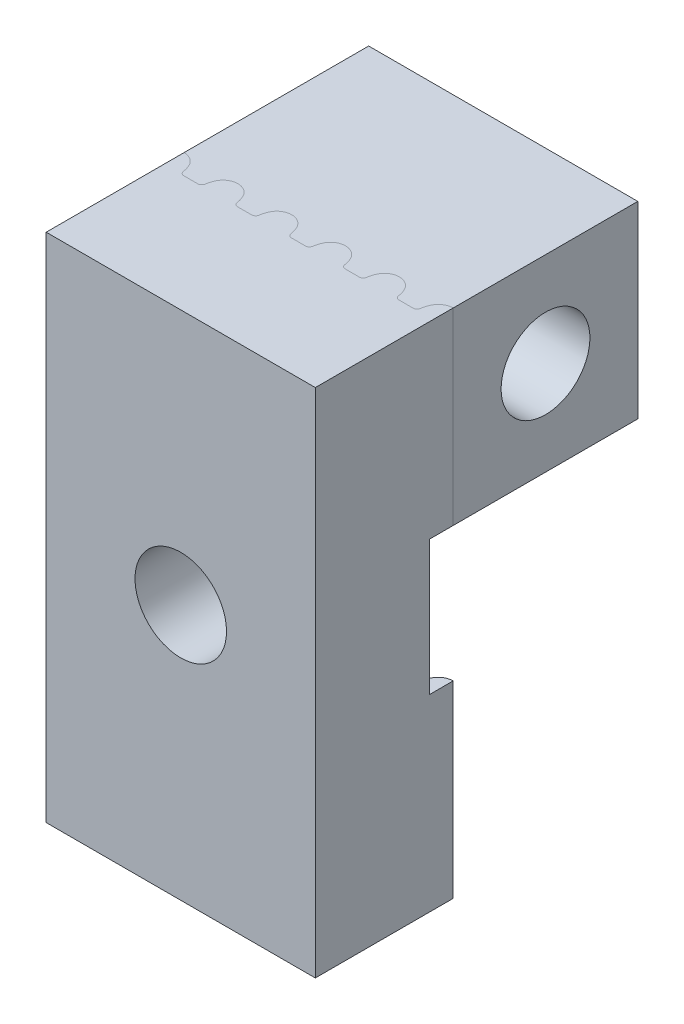
SolidWorks part; units mm, degrees
ref_plane "Front Plane" through (0, 0, 0) normal (0, 0, 1) x (1, 0, 0)
ref_plane "Top Plane" through (0, 0, 0) normal (0, 1, 0) x (1, 0, 0)
ref_plane "Right Plane" through (0, 0, 0) normal (1, 0, 0) x (0, 0, -1)
sketch "Sketch1" plane through (0, 0, 0) normal (0, 0, 1) x (1, 0, 0)
  line L1 (5, 9.5) -> (-5, 9.5)
  line L2 (5, 9.5) -> (5, -9.5)
  line L3 (5, -9.5) -> (-5, -9.5)
  line L4 (-5, 9.5) -> (-5, -9.5)
  line L5 (5, 9.5) -> (-5, -9.5) construction
  line L6 (5, -9.5) -> (-5, 9.5) construction
  point P0 (0, 0)
  dimension "D1" = 10
  dimension "D2" = 19
extrude "Boss-Extrude1" add sketch "Sketch1" along normal blind 4.25
hole_wizard "M3 Clearance Hole1" positions "Sketch3" profile "Sketch4" hole size "M3" standard "ANSI Metric" end condition through all
sketch "Sketch3" plane through (0, 0, 4.25) normal (0, 0, 1) x (1, 0, 0)
  point P0 (0, 0)
sketch "Sketch4" plane through (0, 0, 4.25) normal (1, 0, 0) x (0, -1, 0)
  line L0 (0, 0) -> (0, 4.25)
  line L1 (0, 4.25) -> (1.7, 4.25)
  line L2 (1.7, 4.25) -> (1.7, 0)
  line L5 (1.7, 0) -> (0, 0)
  line L11 (0, -6.35) -> (0, 107.95) construction
  dimension "Thru Hole Dia." = 3.4
  dimension "Thru Hole Depth" = 4.25
sketch "Sketch6" plane through (0, 9.5, 0) normal (0, 1, 0) x (1, 0, 0)
  line L0 (-5, 0) -> (-3, 0)
  line L1 (5, 0) -> (-5, 0) construction
  line L3 (-3.7421, 0.1225) -> (-4.2579, 0.1225)
  line L4 (-5, 0.1225) -> (-5, 0)
  line L5 (-5, 0.1225) -> (-5, 0.8725)
  line L6 (-4, 0) -> (-4, 0.5833) construction
  line L7 (-3, 0.1225) -> (-3, 0)
  line L8 (-3, 0.1225) -> (-3, 0.8725)
  arc A1 (-4.4065, 0.2522) -> (-4.5045, 0.5674) centre (-5.3973, 0.1171) ccw
  arc A2 (-4.5045, 0.5674) -> (-5, 0.8725) centre (-5, 0.3175) ccw
  arc A3 (-4.4065, 0.2522) -> (-4.2579, 0.1225) centre (-4.2579, 0.2725) ccw
  arc A4 (-3.5935, 0.2522) -> (-3.7421, 0.1225) centre (-3.7421, 0.2725) cw
  arc A5 (-3.5935, 0.2522) -> (-3.4955, 0.5674) centre (-2.6027, 0.1171) cw
  arc A6 (-3.4955, 0.5674) -> (-3, 0.8725) centre (-3, 0.3175) cw
  point P17 (-4, 0.1225)
  point P18 (-4, 0)
  dimension "D4" = 0.3
  dimension "D5" = 2
  dimension "D1" = 0.1225
  dimension "D2" = 1
  dimension "D3" = 0.75
  dimension "D6" = 0.1225
extrude "Boss-Extrude2" add sketch "Sketch6" against normal blind 7
pattern_linear "LPattern1" count 5 spacing 2 along (1, 0, 0) of "Boss-Extrude2"
mirror "Mirror1" about plane through (0, 0, 0) normal (0, 1, 0) of "LPattern1"
sketch "Sketch7" plane through (0, -9.5, 0) normal (0, -1, 0) x (1, 0, 0)
  line L5 (-5, -0.8725) -> (-5, -5.8725)
  line L6 (5, -0.8725) -> (5, -5.8725)
  line L7 (-5, -5.8725) -> (5, -5.8725)
  line L8 (-3.7421, -0.1225) -> (-4.2579, -0.1225) construction
  line L9 (-1.7421, -0.1225) -> (-2.2579, -0.1225) construction
  line L10 (0.2579, -0.1225) -> (-0.2579, -0.1225) construction
  line L11 (2.2579, -0.1225) -> (1.7421, -0.1225) construction
  line L12 (4.2579, -0.1225) -> (3.7421, -0.1225) construction
  line L13 (-3.7421, -0.1225) -> (-4.2579, -0.1225)
  line L14 (-1.7421, -0.1225) -> (-2.2579, -0.1225)
  line L15 (0.2579, -0.1225) -> (-0.2579, -0.1225)
  line L16 (2.2579, -0.1225) -> (1.7421, -0.1225)
  line L17 (4.2579, -0.1225) -> (3.7421, -0.1225)
  arc A26 (-5, -0.8725) -> (-4.5045, -0.5674) centre (-5, -0.3175) ccw construction
  arc A27 (-4.5045, -0.5674) -> (-4.4065, -0.2522) centre (-5.3973, -0.1171) ccw construction
  arc A28 (-4.2579, -0.1225) -> (-4.4065, -0.2522) centre (-4.2579, -0.2725) ccw construction
  arc A29 (-3.5935, -0.2522) -> (-3.7421, -0.1225) centre (-3.7421, -0.2725) ccw construction
  arc A30 (-3.5935, -0.2522) -> (-3.4955, -0.5674) centre (-2.6027, -0.1171) ccw construction
  arc A31 (-3.4955, -0.5674) -> (-2.5045, -0.5674) centre (-3, -0.3175) ccw construction
  arc A32 (-2.5045, -0.5674) -> (-2.4065, -0.2522) centre (-3.3973, -0.1171) ccw construction
  arc A33 (-2.2579, -0.1225) -> (-2.4065, -0.2522) centre (-2.2579, -0.2725) ccw construction
  arc A34 (-1.5935, -0.2522) -> (-1.7421, -0.1225) centre (-1.7421, -0.2725) ccw construction
  arc A35 (-1.5935, -0.2522) -> (-1.4955, -0.5674) centre (-0.6027, -0.1171) ccw construction
  arc A36 (-1.4955, -0.5674) -> (-0.5045, -0.5674) centre (-1, -0.3175) ccw construction
  arc A37 (-0.5045, -0.5674) -> (-0.4065, -0.2522) centre (-1.3973, -0.1171) ccw construction
  arc A38 (-0.2579, -0.1225) -> (-0.4065, -0.2522) centre (-0.2579, -0.2725) ccw construction
  arc A39 (0.4065, -0.2522) -> (0.2579, -0.1225) centre (0.2579, -0.2725) ccw construction
  arc A40 (0.4065, -0.2522) -> (0.5045, -0.5674) centre (1.3973, -0.1171) ccw construction
  arc A41 (0.5045, -0.5674) -> (1.4955, -0.5674) centre (1, -0.3175) ccw construction
  arc A42 (1.4955, -0.5674) -> (1.5935, -0.2522) centre (0.6027, -0.1171) ccw construction
  arc A43 (1.7421, -0.1225) -> (1.5935, -0.2522) centre (1.7421, -0.2725) ccw construction
  arc A44 (2.4065, -0.2522) -> (2.2579, -0.1225) centre (2.2579, -0.2725) ccw construction
  arc A45 (2.4065, -0.2522) -> (2.5045, -0.5674) centre (3.3973, -0.1171) ccw construction
  arc A46 (2.5045, -0.5674) -> (3.4955, -0.5674) centre (3, -0.3175) ccw construction
  arc A47 (3.4955, -0.5674) -> (3.5935, -0.2522) centre (2.6027, -0.1171) ccw construction
  arc A48 (3.7421, -0.1225) -> (3.5935, -0.2522) centre (3.7421, -0.2725) ccw construction
  arc A49 (4.4065, -0.2522) -> (4.2579, -0.1225) centre (4.2579, -0.2725) ccw construction
  arc A50 (4.4065, -0.2522) -> (4.5045, -0.5674) centre (5.3973, -0.1171) ccw construction
  arc A51 (4.5045, -0.5674) -> (5, -0.8725) centre (5, -0.3175) ccw construction
  arc A52 (-5, -0.8725) -> (-4.5045, -0.5674) centre (-5, -0.3175) ccw
  arc A53 (-4.5045, -0.5674) -> (-4.4065, -0.2522) centre (-5.3973, -0.1171) ccw
  arc A54 (-4.2579, -0.1225) -> (-4.4065, -0.2522) centre (-4.2579, -0.2725) ccw
  arc A55 (-3.5935, -0.2522) -> (-3.7421, -0.1225) centre (-3.7421, -0.2725) ccw
  arc A56 (-3.5935, -0.2522) -> (-3.4955, -0.5674) centre (-2.6027, -0.1171) ccw
  arc A57 (-3.4955, -0.5674) -> (-2.5045, -0.5674) centre (-3, -0.3175) ccw
  arc A58 (-2.5045, -0.5674) -> (-2.4065, -0.2522) centre (-3.3973, -0.1171) ccw
  arc A59 (-2.2579, -0.1225) -> (-2.4065, -0.2522) centre (-2.2579, -0.2725) ccw
  arc A60 (-1.5935, -0.2522) -> (-1.7421, -0.1225) centre (-1.7421, -0.2725) ccw
  arc A61 (-1.5935, -0.2522) -> (-1.4955, -0.5674) centre (-0.6027, -0.1171) ccw
  arc A62 (-1.4955, -0.5674) -> (-0.5045, -0.5674) centre (-1, -0.3175) ccw
  arc A63 (-0.5045, -0.5674) -> (-0.4065, -0.2522) centre (-1.3973, -0.1171) ccw
  arc A64 (-0.2579, -0.1225) -> (-0.4065, -0.2522) centre (-0.2579, -0.2725) ccw
  arc A65 (0.4065, -0.2522) -> (0.2579, -0.1225) centre (0.2579, -0.2725) ccw
  arc A66 (0.4065, -0.2522) -> (0.5045, -0.5674) centre (1.3973, -0.1171) ccw
  arc A67 (0.5045, -0.5674) -> (1.4955, -0.5674) centre (1, -0.3175) ccw
  arc A68 (1.4955, -0.5674) -> (1.5935, -0.2522) centre (0.6027, -0.1171) ccw
  arc A69 (1.7421, -0.1225) -> (1.5935, -0.2522) centre (1.7421, -0.2725) ccw
  arc A70 (2.4065, -0.2522) -> (2.2579, -0.1225) centre (2.2579, -0.2725) ccw
  arc A71 (2.4065, -0.2522) -> (2.5045, -0.5674) centre (3.3973, -0.1171) ccw
  arc A72 (2.5045, -0.5674) -> (3.4955, -0.5674) centre (3, -0.3175) ccw
  arc A73 (3.4955, -0.5674) -> (3.5935, -0.2522) centre (2.6027, -0.1171) ccw
  arc A74 (3.7421, -0.1225) -> (3.5935, -0.2522) centre (3.7421, -0.2725) ccw
  arc A75 (4.4065, -0.2522) -> (4.2579, -0.1225) centre (4.2579, -0.2725) ccw
  arc A76 (4.4065, -0.2522) -> (4.5045, -0.5674) centre (5.3973, -0.1171) ccw
  arc A77 (4.5045, -0.5674) -> (5, -0.8725) centre (5, -0.3175) ccw
  dimension "D1" = 5
extrude "Boss-Extrude4" add sketch "Sketch7" against normal up to surface (19 mm away) separate body up to face at (0, 9.5, -0.1114)
sketch "Sketch8" plane through (0, 0, -0.1225) normal (0, 0, 1) x (1, 0, 0)
  line L0 (-5, 9.5) -> (-5, -9.5) construction
  line L1 (5, 2.5) -> (-5, 2.5)
  line L2 (5, 2.5) -> (5, -2.5)
  line L3 (5, -2.5) -> (-5, -2.5)
  line L4 (-5, 2.5) -> (-5, -2.5)
  line L5 (5, 2.5) -> (-5, -2.5) construction
  line L6 (5, -2.5) -> (-5, 2.5) construction
  line L7 (-0.5045, 9.5) -> (-1.4955, 9.5) construction
  point P0 (0, 0)
  dimension "D1" = 7
extrude "Cut-Extrude1" cut sketch "Sketch8" against normal blind 0.75
hole_wizard "M3 Clearance Hole2" positions "Sketch10" profile "Sketch11" hole size "M3" standard "ANSI Metric" end condition through all
sketch "Sketch10" plane through (0, 0, -0.8725) normal (0, 0, 1) x (1, 0, 0)
  point P0 (0, 0)
sketch "Sketch11" plane through (0, 0, -0.8725) normal (1, 0, 0) x (0, -1, 0)
  line L0 (0, 0) -> (0, 5)
  line L1 (0, 5) -> (1.7, 5)
  line L2 (1.7, 5) -> (1.7, 0)
  line L5 (1.7, 0) -> (0, 0)
  line L11 (0, -6.35) -> (0, 107.95) construction
  dimension "Thru Hole Dia." = 3.4
  dimension "Thru Hole Depth" = 5
sketch "Sketch12" plane through (0, 0, -0.1225) normal (0, 0, 1) x (1, 0, 0)
  line L1 (-5, 2.5) -> (5, 2.5)
  line L2 (-5, 2.5) -> (-5, -9.5)
  line L3 (-5, -9.5) -> (5, -9.5)
  line L4 (5, 2.5) -> (5, -9.5)
extrude "Cut-Extrude2" cut sketch "Sketch12" against normal up to next (5.75 mm away)
sketch "Sketch13" plane through (0, 0, -5.8725) normal (0, 0, -1) x (-1, 0, 0)
  line L4 (-5, 2.5) -> (5, 2.5)
  line L5 (5, 2.5) -> (5, 9.5)
  line L6 (5, 9.5) -> (-5, 9.5)
  line L7 (-5, 9.5) -> (-5, 2.5)
  line L8 (-5, 2.5) -> (5, 2.5)
  line L9 (5, 2.5) -> (5, 9.5)
  line L10 (5, 9.5) -> (-5, 9.5)
  line L11 (-5, 9.5) -> (-5, 2.5)
  dimension "D1" = 0
extrude "Boss-Extrude5" add sketch "Sketch13" along normal blind 1.86
sketch "Sketch14" plane through (-5, 0, 0) normal (-1, 0, 0) x (0, 0, 1)
  line L0 (-4.3025, 9.5) -> (-4.3025, 2.5) construction
  line L1 (-7.7325, 9.5) -> (-0.8725, 9.5) construction
  line L2 (-7.7325, 2.5) -> (-0.8725, 2.5) construction
  line L3 (-7.7325, 6) -> (-0.8725, 6) construction
  line L4 (-7.7325, 2.5) -> (-7.7325, 9.5) construction
  line L5 (-0.8725, 9.5) -> (-0.8725, 2.5) construction
  circle A0 centre (-4.3025, 6) radius 2.35
  dimension "D1" = 4.7
extrude "Cut-Extrude3" cut sketch "Sketch14" against normal blind 3.8
sketch "Sketch15" plane through (-1.2, 0, 0) normal (-1, 0, 0) x (0, 0, 1)
  circle A0 centre (-4.3025, 6) radius 1.65
  dimension "D1" = 3.3
extrude "Cut-Extrude4" cut sketch "Sketch15" against normal through all
